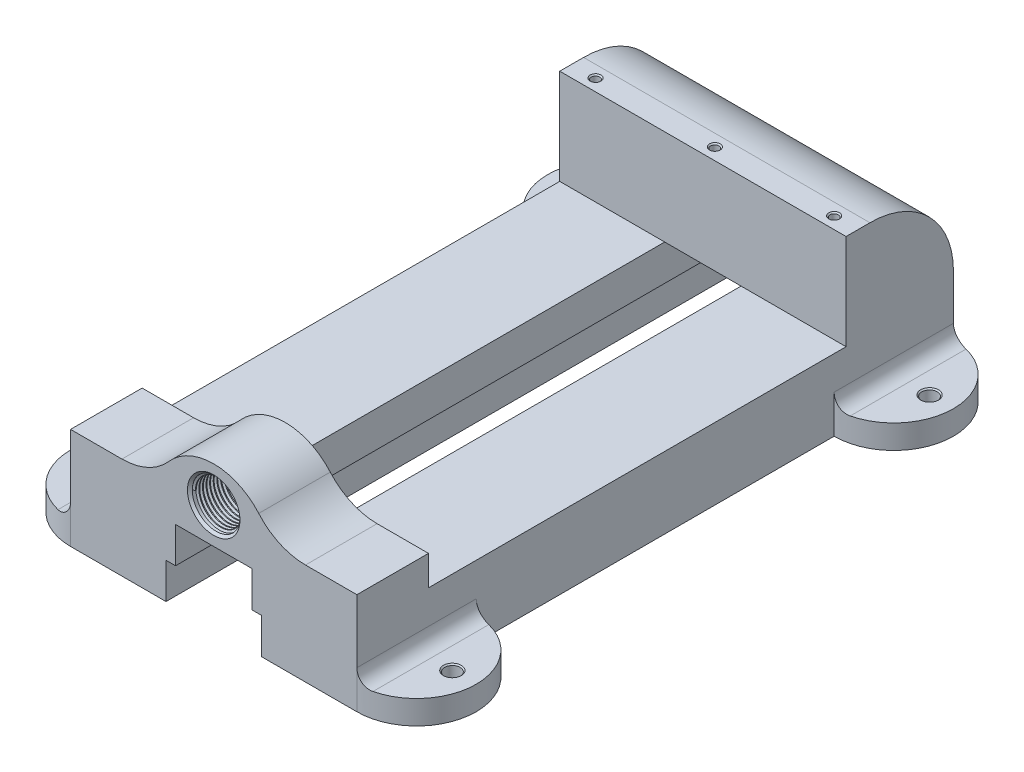
SolidWorks part; units mm, degrees
ref_plane "Front Plane" through (0, 0, 0) normal (0, 0, 1) x (1, 0, 0)
ref_plane "Top Plane" through (0, 0, 0) normal (0, 1, 0) x (1, 0, 0)
ref_plane "Right Plane" through (0, 0, 0) normal (1, 0, 0) x (0, 0, -1)
sketch "Sketch1" plane through (0, 0, 0) normal (0, 1, 0) x (1, 0, 0)
  line L1 (-60, -125) -> (60, -125)
  line L2 (-60, -125) -> (-60, 125)
  line L3 (-60, 125) -> (60, 125)
  line L4 (60, -125) -> (60, 125)
  line L5 (-60, -125) -> (60, 125) construction
  line L6 (-60, 125) -> (60, -125) construction
  point P0 (0, 0)
  dimension "D1" = 120
  dimension "D2" = 250
extrude "Boss-Extrude1" add sketch "Sketch1" along normal blind 70
sketch "Sketch2" plane through (0, 0, 0) normal (0, 1, 0) x (1, 0, 0)
  line L0 (60, -125) -> (60, 125) construction
  line L1 (0, -1000) -> (0, 49000) construction
  line L2 (-1000, 0) -> (49000, 0) construction
  line L3 (60, 125) -> (-60, 125) construction
  line L4 (60, 125) -> (60, 75)
  line L5 (60, -125) -> (60, -75)
  line L6 (-60, -125) -> (-60, -75)
  line L7 (-60, 125) -> (-60, 75)
  arc A0 (60, 125) -> (60, 75) centre (60, 100) cw
  arc A1 (60, -125) -> (60, -75) centre (60, -100) ccw
  arc A2 (-60, -125) -> (-60, -75) centre (-60, -100) cw
  arc A3 (-60, 125) -> (-60, 75) centre (-60, 100) ccw
  dimension "D1" = 25
extrude "Boss-Extrude2" add sketch "Sketch2" along normal blind 10
sketch "Sketch3" plane through (0, 0, 0) normal (1, 0, 0) x (0, 0, -1)
  line L0 (-125, 42.5) -> (-95, 42.5)
  line L1 (-125, 70) -> (-125, 10) construction
  line L2 (-95, 42.5) -> (-95, 30)
  line L3 (-95, 30) -> (80, 30)
  line L4 (80, 30) -> (80, 70)
  line L5 (-125, 70) -> (125, 70) construction
  line L7 (80, 70) -> (90, 70)
  line L8 (125, 70) -> (125, 10) construction
  line L9 (125, 35) -> (125, 0)
  line L18 (-75, 10) -> (-75, 0)
  line L19 (-75, 0) -> (75, 0)
  line L20 (75, 0) -> (75, 10)
  line L21 (75, 10) -> (125, 10)
  line L22 (125, 10) -> (125, 70)
  line L23 (125, 70) -> (-125, 70)
  line L24 (-125, 70) -> (-125, 10)
  line L25 (-125, 10) -> (-75, 10)
  line L26 (-75, 10) -> (-75, 0)
  line L27 (-75, 0) -> (75, 0)
  line L28 (75, 0) -> (75, 10)
  line L29 (75, 10) -> (125, 10)
  line L30 (125, 10) -> (125, 70)
  line L31 (125, 70) -> (-125, 70)
  line L32 (-125, 70) -> (-125, 10)
  line L33 (-125, 10) -> (-75, 10)
  arc A0 (90, 70) -> (125, 35) centre (90, 35) cw
  dimension "D6" = 35
  dimension "D2" = 12.5
  dimension "D3" = 30
  dimension "D4" = 30
  dimension "D5" = 175
  dimension "D1" = 0
extrude "Cut-Extrude2" cut sketch "Sketch3" against normal through all both and the other way through all contours L31 A0 L30 | L31 L32 L0 L2 L3 L4
sketch "Sketch4" plane through (0, 0, 0) normal (0, 0, 1) x (1, 0, 0)
  line L0 (0, -1000) -> (0, 49000) construction
  line L1 (-20, 0) -> (-20, 15)
  line L2 (-60, 0) -> (60, 0) construction
  line L3 (-20, 15) -> (-16, 15)
  line L4 (-16, 15) -> (-16, 30)
  line L5 (-16, 30) -> (16, 30)
  line L6 (16, 15) -> (16, 30)
  line L7 (20, 15) -> (16, 15)
  line L8 (20, 0) -> (20, 15)
  line L9 (-20, 0) -> (20, 0)
  point P12 (0, 30)
  dimension "D1" = 20
  dimension "D2" = 4
  dimension "D3" = 15
  dimension "D4" = 30
extrude "Cut-Extrude3" cut sketch "Sketch4" against normal through all both and the other way through all
sketch "Sketch5" plane through (0, 0, 95) normal (0, 0, -1) x (-1, 0, 0)
  line L3 (23.8485, 42.5) -> (-23.8485, 42.5)
  line L4 (60, 42.5) -> (-60, 42.5) construction
  arc A1 (23.8485, 42.5) -> (-23.8485, 42.5) centre (0, 35) ccw
  dimension "D2" = 50
  dimension "D1" = 35
extrude "Boss-Extrude3" add sketch "Sketch5" against normal up to surface (30 mm away) up to face at (0, 16.0714, 125)
fillet "Fillet1" radius 6 4 edges at (-60, 10, -100) (-60, 10, 100) (60, 10, 100) (60, 10, -100)
fillet "Fillet2" radius 26 2 edges at (23.8485, 42.5, 110) (-23.8485, 42.5, 110)
sketch "Sketch6" plane through (0, 10, 0) normal (0, 1, 0) x (1, 0, 0)
  line L0 (-1000, 0) -> (49000, 0) construction
  line L1 (0, -1000) -> (0, 49000) construction
  circle A0 centre (-75, 100) radius 3.25
  circle A4 centre (75, 100) radius 3.25
  circle A5 centre (-75, -100) radius 3.25
  circle A6 centre (75, -100) radius 3.25
  dimension "D3" = 6.5
  dimension "D1" = 100
  dimension "D2" = 75
extrude "Cut-Extrude4" cut sketch "Sketch6" against normal through all both and the other way through all
sketch "Sketch7" plane through (0, 0, 125) normal (0, 0, 1) x (1, 0, 0)
  circle A0 centre (0, 45) radius 10
  dimension "D2" = 20
  dimension "D1" = 45
extrude "Cut-Extrude5" cut sketch "Sketch7" against normal up to next and the other way through all
sketch "Sketch8" plane through (0, 70, 0) normal (0, 1, 0) x (1, 0, 0)
  line L0 (-1021.1271, 85) -> (48978.8729, 85) construction
  line L1 (16, 80) -> (60, 80) construction
  line L2 (-60, 90) -> (-60, 80) construction
  line L3 (60, 80) -> (60, 90) construction
  circle A0 centre (-50, 85) radius 1.75
  circle A1 centre (0, 85) radius 1.75
  circle A2 centre (50, 85) radius 1.75
  dimension "D1" = 3.5
  dimension "D3" = 10
  dimension "D2" = 5
  dimension "D5" = 10
  dimension "D4" = 3
extrude "Cut-Extrude6" cut sketch "Sketch8" against normal blind 5 contours A1 | A0 | A2
chamfer "Chamfer1" distance 1 angle 45 1 edges at (-10, 45, 125)
chamfer "Chamfer2" distance 0.5 angle 45 7 edges at (-75, 10, -96.75) (-75, 10, 96.75) (75, 10, 103.25) (75, 10, -103.25) (50, 70, -83.25) (0, 70, -83.25) (-50, 70, -83.25)
thread "Thread1" pitch 1.5 start angle 0, offset 0, length 0, pitch 1.5, diameter 20
ref_plane "Plane2" through (-10, 45, 124) normal (0, -1, 0) x (-1, 0, 0)
sketch "Thread Profile2" plane through (-10, 45, 124) normal (0, -1, 0) x (-1, 0, 0)
  line L0 (0, 0) -> (0, 1.5) construction
  line L11 (0, 0) -> (0, 1.3125)
  line L12 (0, 1.3125) -> (-0.8119, 0.8437)
  line L13 (-0.8119, 0.8437) -> (-0.8119, 0.4687)
  line L15 (-0.8119, 0.4687) -> (0, 0)
  line L17 (-0.8119, 0.6562) -> (0, 0.6562) construction
  point P2 (0, 0)
  dimension "Pitch" = 1.5
  dimension "Profile_Angle" = 60
  dimension "Profile_Land" = 0.375
  dimension "Profile_Height" = 0.8119
